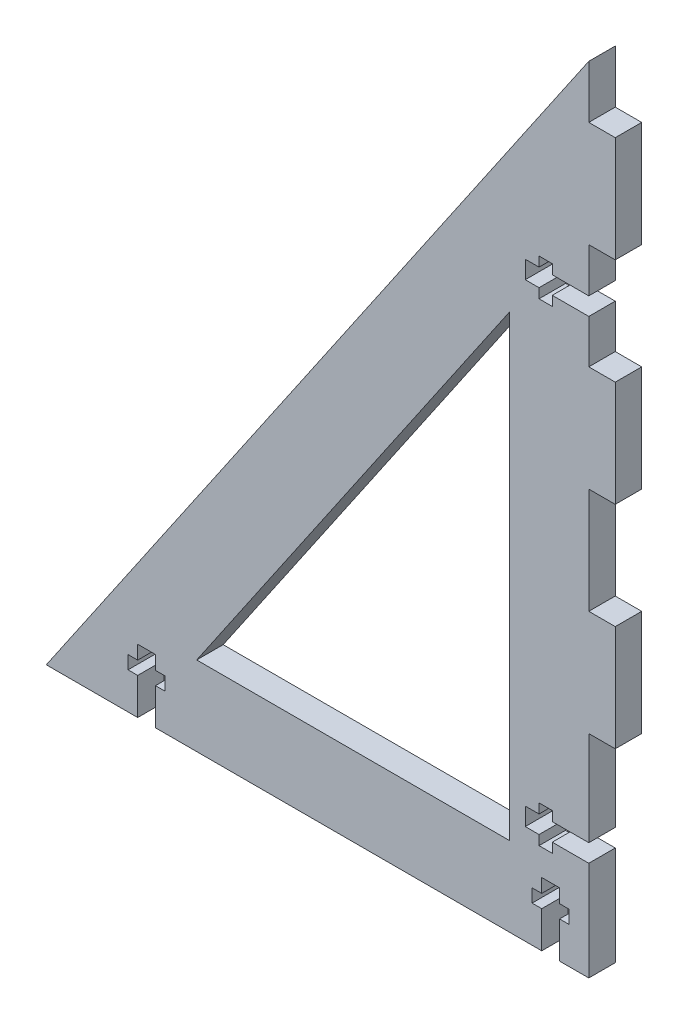
SolidWorks part; units mm, degrees
ref_plane "Front Plane" through (0, 0, 0) normal (0, 0, 1) x (1, 0, 0)
ref_plane "Top Plane" through (0, 0, 0) normal (0, 1, 0) x (1, 0, 0)
ref_plane "Right Plane" through (0, 0, 0) normal (1, 0, 0) x (0, 0, -1)
sketch "Sketch1" plane through (0, 0, 0) normal (0, 0, 1) x (1, 0, 0)
  line L0 (69.85, 285.75) -> (69.85, 95.25)
  line L1 (69.85, 171.45) -> (69.85, 222.25) construction
  line L2 (69.85, 95.25) -> (-60.325, 95.25)
  line L3 (-60.325, 95.25) -> (69.85, 285.75)
  dimension "D1" = 190.5
  dimension "D2" = 130.175
extrude "Boss-Extrude1" add sketch "Sketch1" along normal mid plane 6.35
sketch "Sketch2" plane through (0, 0, 3.175) normal (0, 0, 1) x (1, 0, 0)
  line L9 (-24.2346, 114.3) -> (50.8, 114.3)
  line L10 (50.8, 114.3) -> (50.8, 224.1068)
  line L11 (50.8, 224.1068) -> (-24.2346, 114.3)
  line L12 (-24.2346, 114.3) -> (50.8, 114.3)
  line L13 (50.8, 114.3) -> (50.8, 224.1068)
  line L14 (50.8, 224.1068) -> (-24.2346, 114.3)
  dimension "D1" = 19.05
extrude "Cut-Extrude1" cut sketch "Sketch2" against normal through all
sketch "Sketch3" plane through (0, 0, -3.175) normal (0, 0, -1) x (-1, 0, 0)
  line L0 (-64.5407, 95.25) -> (-36.8762, 95.25) construction
  line L1 (60.325, 95.25) -> (-69.85, 95.25) construction
  line L2 (-69.85, 463.55) -> (-69.85, 6.35) construction
  line L3 (-69.85, 121.2302) -> (-54.61, 121.2302) construction
  line L4 (36.2599, 95.25) -> (36.2599, 110.49) construction
  line L5 (-60.6943, 95.25) -> (-60.6943, 110.49) construction
  line L8 (-69.85, 234.867) -> (-54.61, 234.867) construction
  line B0 (-62.8279, 95.25) -> (-58.5607, 95.25)
  line B1 (-58.5607, 107.188) -> (-56.2493, 107.188)
  line B2 (-56.2493, 107.188) -> (-56.2493, 104.013)
  line B3 (-56.2493, 104.013) -> (-58.5607, 104.013)
  line B4 (-58.5607, 104.013) -> (-58.5607, 95.25)
  line B5 (-58.5607, 107.188) -> (-58.5607, 110.49)
  line B6 (-58.5607, 110.49) -> (-62.8279, 110.49)
  line B7 (-62.8279, 107.188) -> (-62.8279, 110.49)
  line B8 (-62.8279, 104.013) -> (-62.8279, 95.25)
  line B9 (-65.1393, 104.013) -> (-62.8279, 104.013)
  line B10 (-65.1393, 107.188) -> (-65.1393, 104.013)
  line B11 (-62.8279, 107.188) -> (-65.1393, 107.188)
  line B12 (34.1263, 95.25) -> (38.3935, 95.25)
  line B13 (38.3935, 107.188) -> (40.7049, 107.188)
  line B14 (40.7049, 107.188) -> (40.7049, 104.013)
  line B15 (40.7049, 104.013) -> (38.3935, 104.013)
  line B16 (38.3935, 104.013) -> (38.3935, 95.25)
  line B17 (38.3935, 107.188) -> (38.3935, 110.49)
  line B18 (38.3935, 110.49) -> (34.1263, 110.49)
  line B19 (34.1263, 107.188) -> (34.1263, 110.49)
  line B20 (34.1263, 104.013) -> (34.1263, 95.25)
  line B21 (31.8149, 104.013) -> (34.1263, 104.013)
  line B22 (31.8149, 107.188) -> (31.8149, 104.013)
  line B23 (34.1263, 107.188) -> (31.8149, 107.188)
  line B24 (-69.85, 237.0006) -> (-69.85, 232.7334)
  line B25 (-57.912, 232.7334) -> (-57.912, 230.422)
  line B26 (-57.912, 230.422) -> (-61.087, 230.422)
  line B27 (-61.087, 230.422) -> (-61.087, 232.7334)
  line B28 (-61.087, 232.7334) -> (-69.85, 232.7334)
  line B29 (-57.912, 232.7334) -> (-54.61, 232.7334)
  line B30 (-54.61, 232.7334) -> (-54.61, 237.0006)
  line B31 (-57.912, 237.0006) -> (-54.61, 237.0006)
  line B32 (-61.087, 237.0006) -> (-69.85, 237.0006)
  line B33 (-61.087, 239.312) -> (-61.087, 237.0006)
  line B34 (-57.912, 239.312) -> (-61.087, 239.312)
  line B35 (-57.912, 237.0006) -> (-57.912, 239.312)
  line B36 (-69.85, 123.3638) -> (-69.85, 119.0966)
  line B37 (-57.912, 119.0966) -> (-57.912, 116.7852)
  line B38 (-57.912, 116.7852) -> (-61.087, 116.7852)
  line B39 (-61.087, 116.7852) -> (-61.087, 119.0966)
  line B40 (-61.087, 119.0966) -> (-69.85, 119.0966)
  line B41 (-57.912, 119.0966) -> (-54.61, 119.0966)
  line B42 (-54.61, 119.0966) -> (-54.61, 123.3638)
  line B43 (-57.912, 123.3638) -> (-54.61, 123.3638)
  line B44 (-61.087, 123.3638) -> (-69.85, 123.3638)
  line B45 (-61.087, 125.6752) -> (-61.087, 123.3638)
  line B46 (-57.912, 125.6752) -> (-61.087, 125.6752)
  line B47 (-57.912, 123.3638) -> (-57.912, 125.6752)
sketch_block_instance "TSlot-1"
sketch_block "TSlot" parameters "D1"=3.302, "D2"=3.175
sketch_block_instance "TSlot-3"
sketch_block_instance "TSlot-4"
sketch_block_instance "TSlot-5"
extrude "Cut-Extrude2" cut sketch "Sketch3" against normal blind 6.35
sketch "Sketch4" plane through (69.85, 0, 0) normal (1, 0, 0) x (0, 0, -1)
  line L0 (-3.175, 237.0006) -> (-3.175, 285.75) construction
  line L1 (-3.175, 273.05) -> (3.175, 273.05)
  line L2 (-3.175, 273.05) -> (-3.175, 247.65)
  line L3 (-3.175, 247.65) -> (3.175, 247.65)
  line L4 (3.175, 273.05) -> (3.175, 247.65)
  line L5 (3.175, 237.0006) -> (3.175, 285.75) construction
  dimension "D1" = 25.4
  dimension "D2" = 12.7
extrude "Boss-Extrude2" add sketch "Sketch4" along normal blind 6.35
pattern_linear "LPattern1" count 3 spacing 50.8 along (0, -1, 0) of "Boss-Extrude2"
